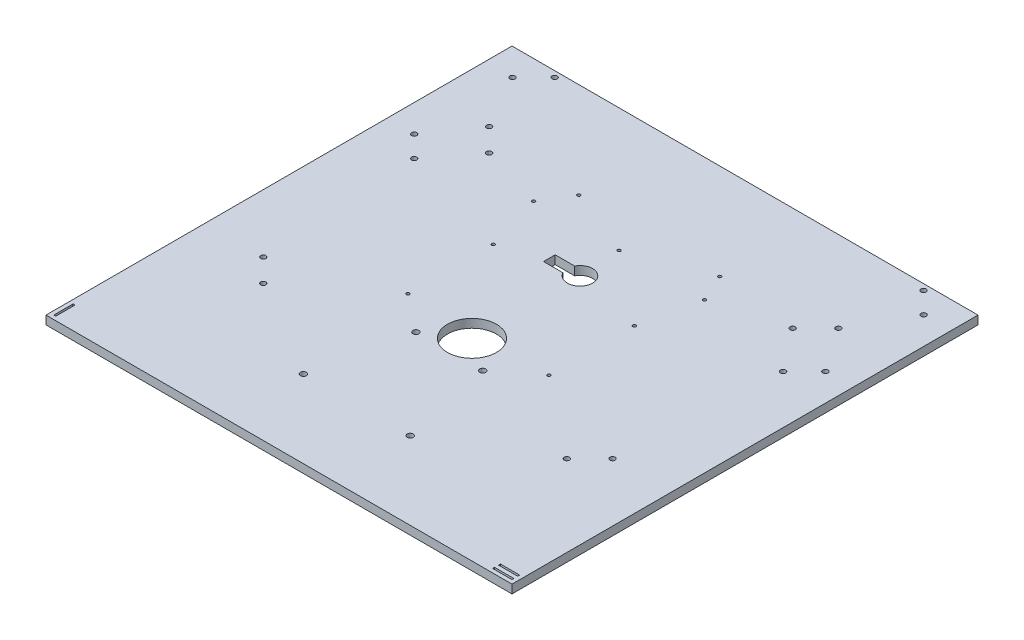
SolidWorks part; units mm, degrees
material "Acrylic (Medium-high impact)"
ref_plane "Front Plane" through (0, 0, 0) normal (0, 0, 1) x (1, 0, 0)
ref_plane "Top Plane" through (0, 0, 0) normal (0, 1, 0) x (1, 0, 0)
ref_plane "Right Plane" through (0, 0, 0) normal (1, 0, 0) x (0, 0, -1)
sketch "Sketch2" plane through (0, 0, 0) normal (0, 1, 0) x (1, 0, 0)
  line L1 (0, 0) -> (304.8, 0)
  line L2 (0, 0) -> (0, 304.8)
  line L3 (0, 304.8) -> (304.8, 304.8)
  line L4 (304.8, 0) -> (304.8, 304.8)
  dimension "D1" = 304.8
  dimension "D2" = 304.8
extrude "Boss-Extrude1" add sketch "Sketch2" along normal blind 5.588
sketch "Sketch4" plane through (0, 5.588, 0) normal (0, 1, 0) x (1, 0, 0)
  line L0 (0, 304.8) -> (0, 0) construction
  line L1 (2.54, 2.54) -> (3.81, 2.54)
  line L2 (2.54, 2.54) -> (2.54, 15.24)
  line L3 (2.54, 15.24) -> (3.81, 15.24)
  line L4 (3.81, 2.54) -> (3.81, 15.24)
  line L5 (2.54, 302.26) -> (3.81, 302.26) construction
  line L6 (2.54, 302.26) -> (2.54, 289.56) construction
  line L7 (2.54, 289.56) -> (3.81, 289.56) construction
  line L8 (3.81, 302.26) -> (3.81, 289.56) construction
  line L9 (6.35, 302.26) -> (7.62, 302.26) construction
  line L10 (6.35, 302.26) -> (6.35, 289.56) construction
  line L11 (6.35, 289.56) -> (7.62, 289.56) construction
  line L12 (7.62, 302.26) -> (7.62, 289.56) construction
  line L13 (304.8, 304.8) -> (0, 304.8) construction
  line L14 (0, 0) -> (304.8, 0) construction
  line L15 (304.8, 0) -> (304.8, 304.8) construction
  line L16 (302.26, 2.54) -> (289.56, 2.54)
  line L17 (302.26, 2.54) -> (302.26, 3.81)
  line L18 (302.26, 3.81) -> (289.56, 3.81)
  line L19 (289.56, 2.54) -> (289.56, 3.81)
  line L20 (302.26, 6.35) -> (289.56, 6.35)
  line L21 (302.26, 6.35) -> (302.26, 7.62)
  line L22 (302.26, 7.62) -> (289.56, 7.62)
  line L23 (289.56, 6.35) -> (289.56, 7.62)
  dimension "D1" = 12.7
  dimension "D2" = 1.27
  dimension "D3" = 2.54
  dimension "D4" = 2.54
  dimension "D5" = 2.54
  dimension "D6" = 2.54
  dimension "D7" = 2.54
  dimension "D8" = 2.54
  dimension "D9" = 2.54
  dimension "D10" = 2.54
extrude "Cut-Extrude1" cut sketch "Sketch4" against normal through all
sketch "Sketch5" plane through (0, 5.588, 0) normal (0, 1, 0) x (1, 0, 0)
  line L0 (0, 304.8) -> (0, 0) construction
  line L1 (34.5465, 268.1122) -> (263.4005, 268.1122)
  line L2 (34.5465, 268.1122) -> (34.5465, 281.0662)
  line L3 (34.5465, 281.0662) -> (263.4005, 281.0662)
  line L4 (263.4005, 268.1122) -> (263.4005, 281.0662)
  line L5 (304.8, 0) -> (304.8, 304.8) construction
  line L6 (304.8, 304.8) -> (0, 304.8) construction
  dimension "D1" = 34.5465
  dimension "D2" = 41.3995
  dimension "D3" = 23.7338
  dimension "D4" = 12.954
extrude "Cut-Extrude2" cut sketch "Sketch5" against normal blind 0.254
sketch "Sketch6" plane through (0, 5.588, 0) normal (0, 1, 0) x (1, 0, 0)
  circle A0 centre (152.48, 126.1263) radius 15.748 construction
  circle A1 centre (152.48, 126.1263) radius 15.748 construction
  circle A2 centre (152.48, 126.1263) radius 16.002
  circle A3 centre (31.75, 300.9591) radius 1.7 construction
  circle A4 centre (17.9387, 287.1479) radius 1.7 construction
  circle A5 centre (273.05, 300.9591) radius 1.7 construction
  circle A6 centre (286.8612, 287.1479) radius 1.7 construction
  circle A7 centre (286.8613, 222.9062) radius 1.7 construction
  circle A8 centre (273.05, 209.095) radius 1.7 construction
  circle A9 centre (31.75, 209.095) radius 1.7 construction
  circle A10 centre (17.9388, 222.9062) radius 1.7 construction
  circle A11 centre (31.75, 300.9591) radius 1.7
  circle A12 centre (17.9387, 287.1479) radius 1.7
  circle A13 centre (273.05, 300.9591) radius 1.7
  circle A14 centre (286.8612, 287.1479) radius 1.7
  circle A15 centre (286.8613, 222.9062) radius 1.7
  circle A16 centre (273.05, 209.095) radius 1.7
  circle A17 centre (31.75, 209.095) radius 1.7
  circle A18 centre (17.9388, 222.9062) radius 1.7
  circle A19 centre (38.1788, 103.933) radius 1.7 construction
  circle A20 centre (53.133, 88.9788) radius 1.7 construction
  circle A21 centre (251.667, 88.9788) radius 1.7 construction
  circle A22 centre (266.6212, 103.933) radius 1.7 construction
  circle A23 centre (266.6212, 251.667) radius 1.7 construction
  circle A24 centre (251.667, 236.7127) radius 1.7 construction
  circle A25 centre (53.133, 236.7127) radius 1.7 construction
  circle A26 centre (38.1788, 251.667) radius 1.7 construction
  circle A27 centre (38.1788, 103.933) radius 1.7
  circle A28 centre (53.133, 88.9788) radius 1.7
  circle A29 centre (251.667, 88.9788) radius 1.7
  circle A30 centre (266.6212, 103.933) radius 1.7
  circle A31 centre (266.6212, 251.667) radius 1.7
  circle A32 centre (251.667, 236.7127) radius 1.7
  circle A33 centre (53.133, 236.7127) radius 1.7
  circle A34 centre (38.1788, 251.667) radius 1.7
  circle A35 centre (117.555, 50.8216) radius 4.5 construction
  circle A36 centre (187.405, 50.8216) radius 4.5 construction
  circle A37 centre (174.3081, 111.328) radius 4.5 construction
  circle A38 centre (130.6519, 111.328) radius 4.5 construction
  circle A39 centre (117.555, 50.8216) radius 4.5 construction
  circle A40 centre (187.405, 50.8216) radius 4.5 construction
  circle A41 centre (174.3081, 111.328) radius 4.5 construction
  circle A42 centre (130.6519, 111.328) radius 4.5 construction
  circle A43 centre (130.6519, 111.328) radius 1.96
  circle A44 centre (174.3081, 111.328) radius 1.96
  circle A45 centre (187.405, 50.8216) radius 1.96
  circle A46 centre (117.555, 50.8216) radius 1.96
  dimension "D1" = 0.254
  dimension "D2" = 2.54
extrude "Cut-Extrude3" cut sketch "Sketch6" against normal through all
sketch "Sketch7" plane through (0, 5.588, 0) normal (0, 1, 0) x (1, 0, 0)
  line L0 (152.4, 304.8) -> (152.4, 0) construction
  line L1 (304.8, 304.8) -> (0, 304.8) construction
  line L2 (0, 0) -> (304.8, 0) construction
  line L4 (145.0768, 200.66) -> (132.3768, 200.66)
  line L5 (145.0768, 200.66) -> (145.0768, 193.04) construction
  line L6 (145.0768, 193.04) -> (132.3768, 193.04)
  line L7 (132.3768, 200.66) -> (132.3768, 193.04)
  circle A0 centre (152.4, 196.85) radius 8.255 construction
  arc A1 (145.0768, 200.66) -> (145.0768, 193.04) centre (152.4, 196.85) cw
  dimension "D2" = 16.51
  dimension "D1" = 107.95
  dimension "D3" = 7.62
  dimension "D4" = 12.7
extrude "Cut-Extrude4" cut sketch "Sketch7" against normal through all
sketch "Sketch8" plane through (0, 5.588, 0) normal (0, 1, 0) x (1, 0, 0)
  circle A0 centre (94.94, 223.995) radius 0.762 construction
  circle A1 centre (150.82, 223.995) radius 0.762 construction
  circle A2 centre (206.7, 223.995) radius 0.762 construction
  circle A3 centre (94.94, 223.995) radius 0.762 construction
  circle A4 centre (150.82, 223.995) radius 0.762 construction
  circle A5 centre (206.7, 223.995) radius 0.762 construction
  circle A6 centre (206.7, 223.995) radius 1.016
  circle A7 centre (150.82, 223.995) radius 1.016
  circle A8 centre (94.94, 223.995) radius 1.016
  dimension "D1" = 0.254
extrude "Cut-Extrude5" cut sketch "Sketch8" against normal through all
sketch "Sketch9" plane through (0, 5.588, 0) normal (0, 1, 0) x (1, 0, 0)
  circle A0 centre (106.3, 242.18) radius 0.762 construction
  circle A1 centre (106.3, 186.3) radius 0.762 construction
  circle A2 centre (106.3, 130.42) radius 0.762 construction
  circle A3 centre (198.5, 130.42) radius 0.762 construction
  circle A4 centre (198.5, 186.3) radius 0.762 construction
  circle A5 centre (198.5, 242.18) radius 0.762 construction
  circle A6 centre (106.3, 242.18) radius 0.762 construction
  circle A7 centre (106.3, 186.3) radius 0.762 construction
  circle A8 centre (106.3, 130.42) radius 0.762 construction
  circle A9 centre (198.5, 130.42) radius 0.762 construction
  circle A10 centre (198.5, 186.3) radius 0.762 construction
  circle A11 centre (198.5, 242.18) radius 0.762 construction
  circle A12 centre (106.3, 242.18) radius 1.016
  circle A13 centre (106.3, 186.3) radius 1.016
  circle A14 centre (106.3, 130.42) radius 1.016
  circle A15 centre (198.5, 130.42) radius 1.016
  circle A16 centre (198.5, 186.3) radius 1.016
  circle A17 centre (198.5, 242.18) radius 1.016
  dimension "D1" = 0.254
extrude "Cut-Extrude6" cut sketch "Sketch9" against normal through all
sketch "Sketch10" plane through (0, 5.588, 0) normal (0, 1, 0) x (1, 0, 0)
  line L1 (30.0638, 287.1688) -> (266.0755, 287.1688)
  line L2 (30.0638, 287.1688) -> (30.0638, 264.2232)
  line L3 (30.0638, 264.2232) -> (266.0755, 264.2232)
  line L4 (266.0755, 287.1688) -> (266.0755, 264.2232)
extrude "Boss-Extrude3" add sketch "Sketch10" against normal through all
equation "\"D8@Sketch4\"=\"D6@Sketch4\""
